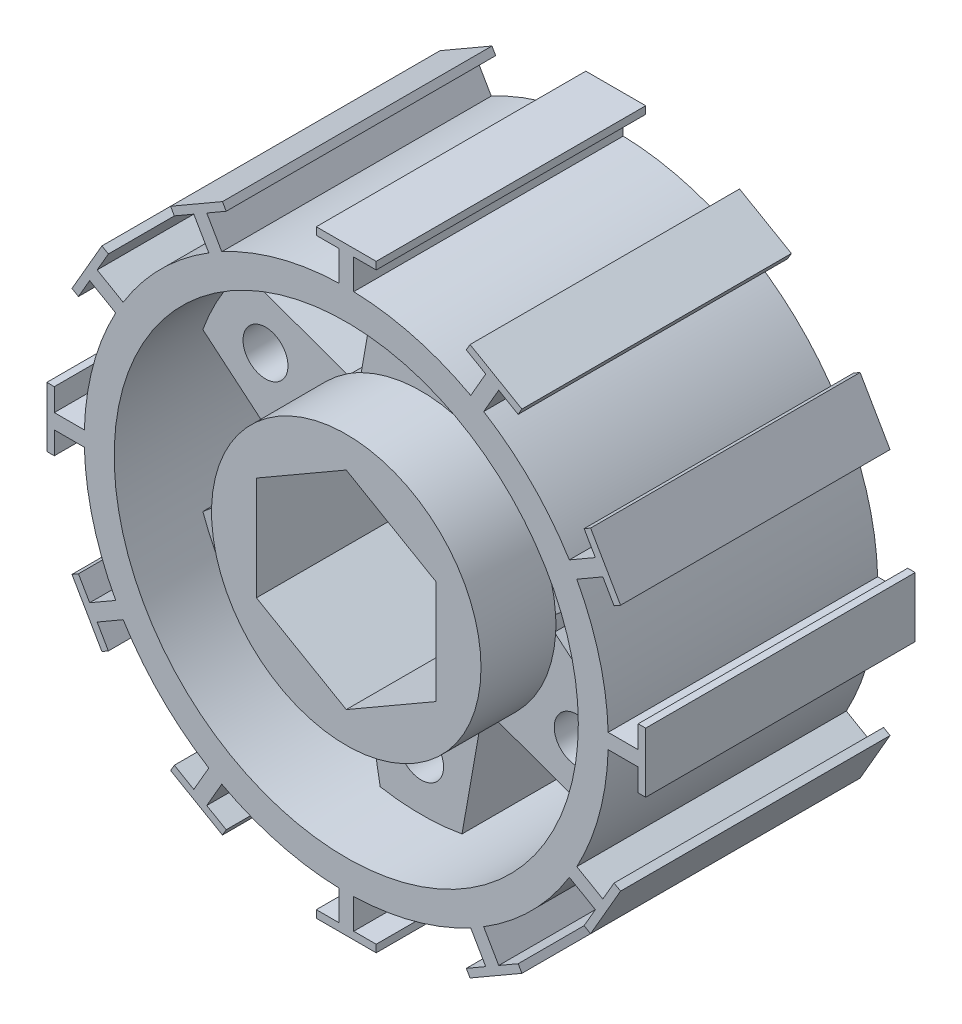
SolidWorks part; units mm, degrees
material "ABS"
ref_plane "前视基准面" through (0, 0, 0) normal (0, 0, 1) x (1, 0, 0)
ref_plane "上视基准面" through (0, 0, 0) normal (0, 1, 0) x (1, 0, 0)
ref_plane "右视基准面" through (0, 0, 0) normal (1, 0, 0) x (0, 0, -1)
sketch "草图1" plane through (0, 0, 0) normal (0, 0, 1) x (1, 0, 0)
  circle A0 centre (0, 0) radius 27
  dimension "D1" = 54
extrude "凸台-拉伸1" add sketch "草图1" along normal mid plane 20
fillet "圆角1" radius 2 2 edges at (27, 0, -10) (27, 0, 10)
sketch "草图2" plane through (0, 0, 10) normal (0, 0, 1) x (1, 0, 0)
  circle A0 centre (0, 0) radius 15.5
  dimension "D1" = 31
extrude "切除-拉伸2" cut sketch "草图2" against normal blind 6 contours A0
sketch "草图4" plane through (0, 0, 4) normal (0, 0, 1) x (1, 0, 0)
  circle A0 centre (0, 0) radius 9
  dimension "D1" = 18
extrude "凸台-拉伸2" add sketch "草图4" along normal blind 5
sketch "草图5" plane through (0, 0, 9) normal (0, 0, 1) x (1, 0, 0)
  line L1 (0, 6.9282) -> (-6, 3.4641)
  line L2 (-6, 3.4641) -> (-6, -3.4641)
  line L3 (-6, -3.4641) -> (0, -6.9282)
  line L4 (0, -6.9282) -> (6, -3.4641)
  line L5 (6, -3.4641) -> (6, 3.4641)
  line L6 (6, 3.4641) -> (0, 6.9282)
  circle A0 centre (0, 0) radius 6 construction
  dimension "D1" = 12
extrude "切除-拉伸3" cut sketch "草图5" against normal blind 10
sketch "草图6" plane through (0, 0, -1) normal (0, 0, 1) x (1, 0, 0)
  circle A0 centre (0, 0) radius 1.5
  dimension "D1" = 3
extrude "切除-拉伸4" cut sketch "草图6" against normal through all
sketch "草图8" plane through (0, 0, -10) normal (0, 0, -1) x (-1, 0, 0)
  circle A0 centre (0, 0) radius 15.5
  dimension "D1" = 31
extrude "切除-拉伸5" cut sketch "草图8" against normal blind 4
sketch "草图9" plane through (0, 0, 4) normal (0, 0, 1) x (1, 0, 0)
  line L0 (-39.4745, 0) -> (50.3501, 0) construction
  line L1 (-8.9047, 0.5) -> (-14.5796, 5.2618)
  line L2 (-8.9047, -0.5) -> (-14.5796, -5.2618)
  arc A0 (-8.9047, 0.5) -> (-8.9047, -0.5) centre (0, 0) ccw
  circle A1 centre (0, 0) radius 15.5 construction
  arc A2 (-14.5796, -5.2618) -> (-14.5796, 5.2618) centre (0, 0) cw
  dimension "D1" = 0.5
  dimension "D2" = 40
extrude "切除-拉伸8" cut sketch "草图9" against normal through all
sketch "草图10" plane through (0, 0, 4) normal (0, 0, 1) x (1, 0, 0)
  circle A0 centre (0, 12) radius 1.5
  dimension "D1" = 3
  dimension "D2" = 12
extrude "切除-拉伸9" cut sketch "草图10" against normal through all
pattern_circular "阵列(圆周)2" count 6 over 360 about axis through (0, 0, 10) along (0, 0, -1) of "切除-拉伸8", "切除-拉伸9"
sketch "草图11" plane through (0, 0, -6) normal (0, 0, -1) x (-1, 0, 0)
  circle A0 centre (0, 0) radius 5
  dimension "D1" = 10
extrude "切除-拉伸10" cut sketch "草图11" against normal blind 2
fillet "圆角2" radius 1 1 edges at (-5, 0, -6)
sketch "草图12" plane through (0, 0, 10) normal (0, 0, 1) x (1, 0, 0)
  circle A0 centre (0, 0) radius 17.5
  circle A1 centre (0, 0) radius 15.5 construction
  dimension "D1" = 2
extrude "切除-拉伸11" cut sketch "草图12" against normal blind 20 flip side to cut
sketch "草图13" plane through (0, 0, 0) normal (0, 0, 1) x (1, 0, 0)
  line L0 (0, -26.7817) -> (0, 22.2616) construction
  line L1 (0.5, 17.4929) -> (0.5, 19.5)
  line L2 (0.5, 19.5) -> (2, 19.5)
  line L3 (-2, 19.5) -> (-2, 20)
  line L4 (2, 19.5) -> (2, 20)
  line L5 (2, 20) -> (-2, 20)
  line L6 (-0.5, 19.5) -> (-2, 19.5)
  line L7 (-0.5, 17.4929) -> (-0.5, 19.5)
  circle A0 centre (0, 0) radius 17.5 construction
  arc A1 (0.5, 17.4929) -> (-0.5, 17.4929) centre (0, 0) ccw
  point P12 (0, 17.5)
  point P14 (0, 20)
  dimension "D1" = 0.5
  dimension "D2" = 0.5
  dimension "D3" = 2.5
  dimension "D4" = 2
extrude "凸台-拉伸3" add sketch "草图13" along normal mid plane 20
pattern_circular "阵列(圆周)3" count 12 over 360 about axis through (0, 0, -10) along (0, 0, 1) of "凸台-拉伸3"
sketch "草图15" plane through (0, 0, -10) normal (0, 0, -1) x (-1, 0, 0)
  circle A0 centre (0, 0) radius 32.0276
extrude "切除-拉伸12" cut sketch "草图15" against normal blind 1
sketch "草图16" plane through (0, 0, 10) normal (0, 0, 1) x (1, 0, 0)
  circle A0 centre (0, 0) radius 25.8085
extrude "切除-拉伸13" cut sketch "草图16" against normal blind 1
